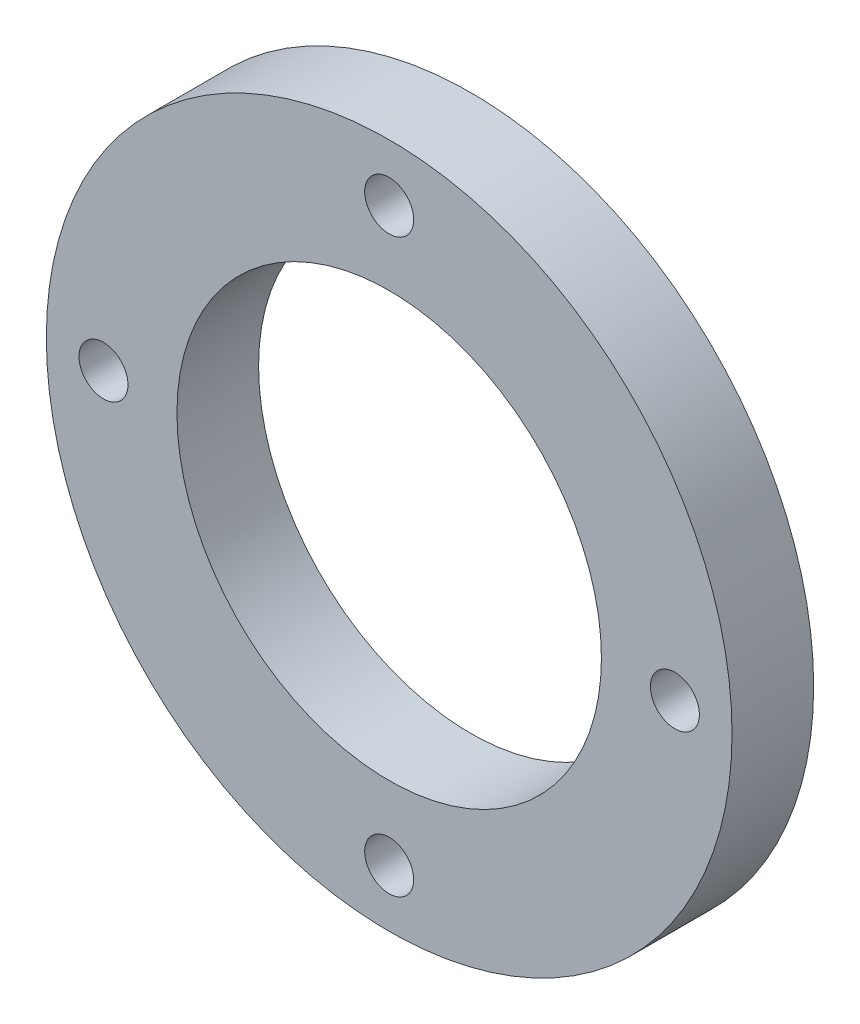
SolidWorks part; units mm, degrees
material "Thornel Mat VMA"
ref_plane "Front Plane" through (0, 0, 0) normal (0, 0, 1) x (1, 0, 0)
ref_plane "Top Plane" through (0, 0, 0) normal (0, 1, 0) x (1, 0, 0)
ref_plane "Right Plane" through (0, 0, 0) normal (1, 0, 0) x (0, 0, -1)
sketch "Sketch1" plane through (0, 0, 0) normal (0, 0, 1) x (1, 0, 0)
  circle A0 centre (49, 5) radius 13 construction
  circle A1 centre (31.5, 5) radius 1.5 construction
  circle A2 centre (49, 22.5) radius 1.5 construction
  circle A3 centre (66.5, 5) radius 1.5 construction
  circle A4 centre (49, -12.5) radius 1.5 construction
  circle A5 centre (49, 5) radius 13
  circle A6 centre (31.5, 5) radius 1.5
  circle A7 centre (49, 22.5) radius 1.5
  circle A8 centre (66.5, 5) radius 1.5
  circle A9 centre (49, -12.5) radius 1.5
  arc A10 (49, -16) -> (49, 26) centre (49, 5) ccw construction
  circle A11 centre (49, 5) radius 21
  point P18 (48.4684, 26)
extrude "Boss-Extrude1" add sketch "Sketch1" along normal blind 5
